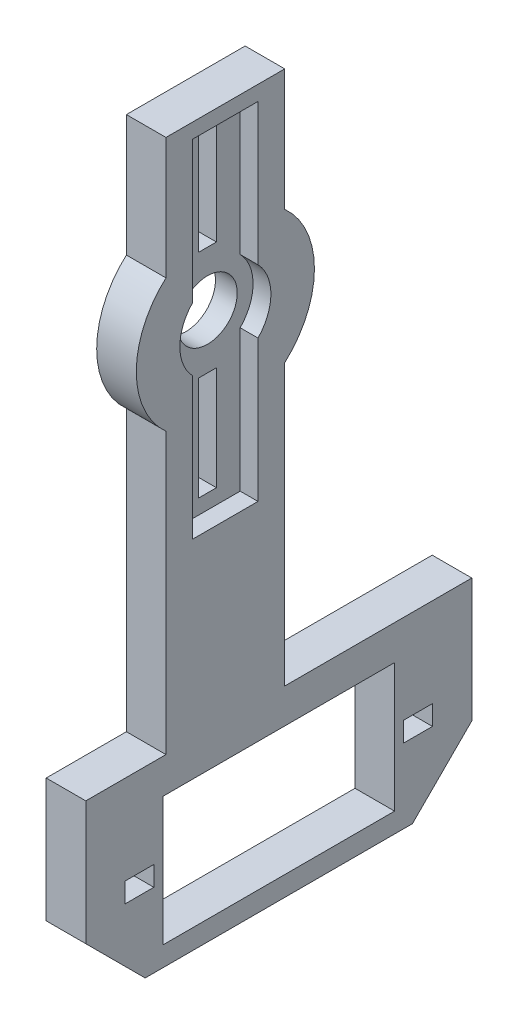
SolidWorks part; units mm, degrees
ref_plane "Front Plane" through (0, 0, 0) normal (0, 0, 1) x (1, 0, 0)
ref_plane "Top Plane" through (0, 0, 0) normal (0, 1, 0) x (1, 0, 0)
ref_plane "Right Plane" through (0, 0, 0) normal (1, 0, 0) x (0, 0, -1)
sketch "Sketch1" plane through (0, 0, 0) normal (1, 0, 0) x (0, 0, -1)
  circle A0 centre (-66, -20) radius 9
extrude "Boss-Extrude1" add sketch "Sketch1" along normal blind 4 from offset 70.4 offset against normal yes
sketch "Sketch2" plane through (0, 0, 0) normal (0, 0, 1) x (1, 0, 0)
  line L1 (-70.4, -56) -> (-66.4, -56)
  line L2 (-70.4, -56) -> (-70.4, -1)
  line L3 (-70.4, -1) -> (-66.4, -1)
  line L4 (-66.4, -56) -> (-66.4, -1)
extrude "Boss-Extrude2" add sketch "Sketch2" along normal blind 12 from offset 60
sketch "Sketch3" plane through (0, 0, 0) normal (0, 0, 1) x (1, 0, 0)
  line L1 (-70.4, -73.5) -> (-66.4, -73.5)
  line L2 (-70.4, -73.5) -> (-70.4, -55)
  line L3 (-70.4, -55) -> (-66.4, -55)
  line L4 (-66.4, -73.5) -> (-66.4, -55)
extrude "Boss-Extrude3" add sketch "Sketch3" along normal blind 39 from offset 41.1
sketch "Sketch4" plane through (0, 0, 0) normal (1, 0, 0) x (0, 0, -1)
  line L0 (-81.1, -74.5) -> (-73.1, -74.5)
  line L1 (-73.1, -74.5) -> (-81.1, -66.5)
  line L2 (-81.1, -66.5) -> (-81.1, -74.5)
extrude "Boss-Extrude4" add sketch "Sketch4" along normal blind 6 from offset 71.4 separate body offset against normal yes
combine bodies "Combine1" operation type subtract main body 103 bodies to subtract 104
sketch "Sketch5" plane through (0, 0, 0) normal (1, 0, 0) x (0, 0, -1)
  line L0 (-40.1, -74.5) -> (-48.1, -74.5)
  line L1 (-48.1, -74.5) -> (-40.1, -66.5)
  line L2 (-40.1, -66.5) -> (-40.1, -74.5)
extrude "Boss-Extrude5" add sketch "Sketch5" along normal blind 6 from offset 71.4 separate body offset against normal yes
combine bodies "Combine2" operation type subtract main body 105 bodies to subtract 106
sketch "Sketch6" plane through (0, 0, 0) normal (1, 0, 0) x (0, 0, -1)
  circle A0 centre (-66, -20) radius 4.6
extrude "Boss-Extrude6" add sketch "Sketch6" along normal blind 2.3 from offset 68.2 separate body offset against normal yes
combine bodies "Combine3" operation type subtract main body 107 bodies to subtract 108
sketch "Sketch7" plane through (0, 0, 0) normal (0, 0, 1) x (1, 0, 0)
  line L1 (-68.2, -20) -> (-65.9, -20)
  line L2 (-68.2, -20) -> (-68.2, -2.5)
  line L3 (-68.2, -2.5) -> (-65.9, -2.5)
  line L4 (-65.9, -20) -> (-65.9, -2.5)
extrude "Boss-Extrude7" add sketch "Sketch7" along normal blind 6.6 from offset 62.7 separate body
combine bodies "Combine4" operation type subtract main body 109 bodies to subtract 110
sketch "Sketch8" plane through (0, 0, 0) normal (0, 0, 1) x (1, 0, 0)
  line L1 (-71.4, -14.5) -> (-65.4, -14.5)
  line L2 (-71.4, -14.5) -> (-71.4, -4)
  line L3 (-71.4, -4) -> (-65.4, -4)
  line L4 (-65.4, -14.5) -> (-65.4, -4)
extrude "Boss-Extrude8" add sketch "Sketch8" along normal blind 1.8 from offset 65.1 separate body
combine bodies "Combine5" operation type subtract main body 111 bodies to subtract 112
sketch "Sketch9" plane through (0, 0, 0) normal (0, 0, 1) x (1, 0, 0)
  line L1 (-68.2, -37.5) -> (-65.9, -37.5)
  line L2 (-68.2, -37.5) -> (-68.2, -20)
  line L3 (-68.2, -20) -> (-65.9, -20)
  line L4 (-65.9, -37.5) -> (-65.9, -20)
extrude "Boss-Extrude9" add sketch "Sketch9" along normal blind 6.6 from offset 62.7 separate body
combine bodies "Combine6" operation type subtract main body 113 bodies to subtract 114
sketch "Sketch10" plane through (0, 0, 0) normal (0, 0, 1) x (1, 0, 0)
  line L1 (-71.4, -36) -> (-65.4, -36)
  line L2 (-71.4, -36) -> (-71.4, -25.5)
  line L3 (-71.4, -25.5) -> (-65.4, -25.5)
  line L4 (-65.4, -36) -> (-65.4, -25.5)
extrude "Boss-Extrude10" add sketch "Sketch10" along normal blind 1.8 from offset 65.1 separate body
combine bodies "Combine7" operation type subtract main body 115 bodies to subtract 116
sketch "Sketch11" plane through (0, 0, 0) normal (1, 0, 0) x (0, 0, -1)
  circle A0 centre (-66, -20) radius 3
extrude "Boss-Extrude11" add sketch "Sketch11" along normal blind 6 from offset 71.4 separate body offset against normal yes
combine bodies "Combine8" operation type subtract main body 117 bodies to subtract 118
sketch "Sketch12" plane through (0, 0, 0) normal (0, 0, 1) x (1, 0, 0)
  line L1 (-71.4, -71.5) -> (-65.4, -71.5)
  line L2 (-71.4, -71.5) -> (-71.4, -58.5)
  line L3 (-71.4, -58.5) -> (-65.4, -58.5)
  line L4 (-65.4, -71.5) -> (-65.4, -58.5)
extrude "Boss-Extrude12" add sketch "Sketch12" along normal blind 23.4 from offset 48.9 separate body
combine bodies "Combine9" operation type subtract main body 119 bodies to subtract 120
sketch "Sketch13" plane through (0, 0, 0) normal (0, 0, 1) x (1, 0, 0)
  line L1 (-71.4, -66) -> (-65.4, -66)
  line L2 (-71.4, -66) -> (-71.4, -64)
  line L3 (-71.4, -64) -> (-65.4, -64)
  line L4 (-65.4, -66) -> (-65.4, -64)
extrude "Boss-Extrude13" add sketch "Sketch13" along normal blind 2.9 from offset 45.075 separate body
combine bodies "Combine10" operation type subtract main body 121 bodies to subtract 122
sketch "Sketch14" plane through (0, 0, 0) normal (0, 0, 1) x (1, 0, 0)
  line L1 (-71.4, -66) -> (-65.4, -66)
  line L2 (-71.4, -66) -> (-71.4, -64)
  line L3 (-71.4, -64) -> (-65.4, -64)
  line L4 (-65.4, -66) -> (-65.4, -64)
extrude "Boss-Extrude14" add sketch "Sketch14" along normal blind 2.9 from offset 73.225 separate body
combine bodies "Combine11" operation type subtract main body 123 bodies to subtract 124
